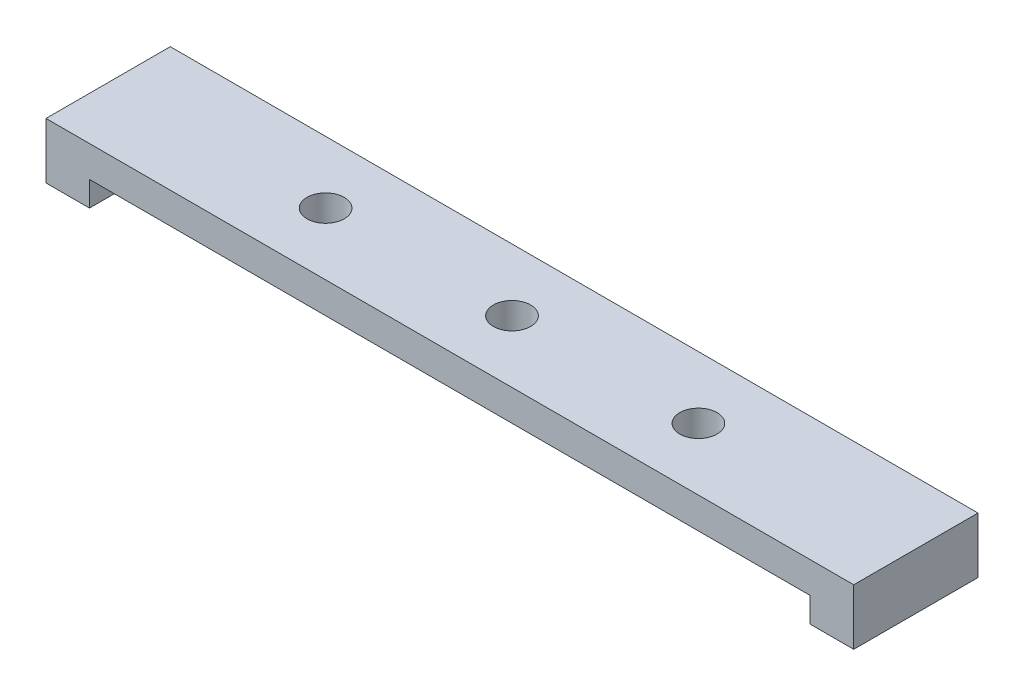
SolidWorks part; units mm, degrees
material "1060 Alloy"
ref_plane "Front Plane" through (0, 0, 0) normal (0, 0, 1) x (1, 0, 0)
ref_plane "Top Plane" through (0, 0, 0) normal (0, 1, 0) x (1, 0, 0)
ref_plane "Right Plane" through (0, 0, 0) normal (1, 0, 0) x (0, 0, -1)
sketch "Sketch1" plane through (0, 0, 0) normal (0, 1, 0) x (1, 0, 0)
  line L0 (32.5, 5) -> (32.5, 10) construction
  line L1 (0, 0) -> (65, 0)
  line L2 (0, 0) -> (0, 10)
  line L3 (0, 10) -> (65, 10)
  line L4 (65, 0) -> (65, 10)
  circle A0 centre (17.5, 5) radius 1.5
  circle A1 centre (32.5, 5) radius 1.5
  circle A2 centre (47.5, 5) radius 1.5
  dimension "D3" = 3
  dimension "D4" = 5
  dimension "D5" = 15
  dimension "D1" = 10
  dimension "D2" = 65
  dimension "D6" = 15
extrude "Boss-Extrude1" add sketch "Sketch1" along normal blind 4.5
sketch "Sketch2" plane through (0, 0, 0) normal (0, -1, 0) x (1, 0, 0)
  line L0 (0, 0) -> (65, 0) construction
  line L1 (3.5, 0) -> (61.5, 0)
  line L2 (3.5, 0) -> (3.5, -10)
  line L3 (3.5, -10) -> (61.5, -10)
  line L4 (61.5, 0) -> (61.5, -10)
  line L5 (65, -10) -> (0, -10) construction
  line L6 (0, -10) -> (0, 0) construction
  line L7 (65, 0) -> (65, -10) construction
  dimension "D1" = 3.5
  dimension "D2" = 3.5
extrude "Cut-Extrude1" cut sketch "Sketch2" against normal offset from surface (2 mm away) 2.5 up to face at (32.5, 4.5, -3.5)
